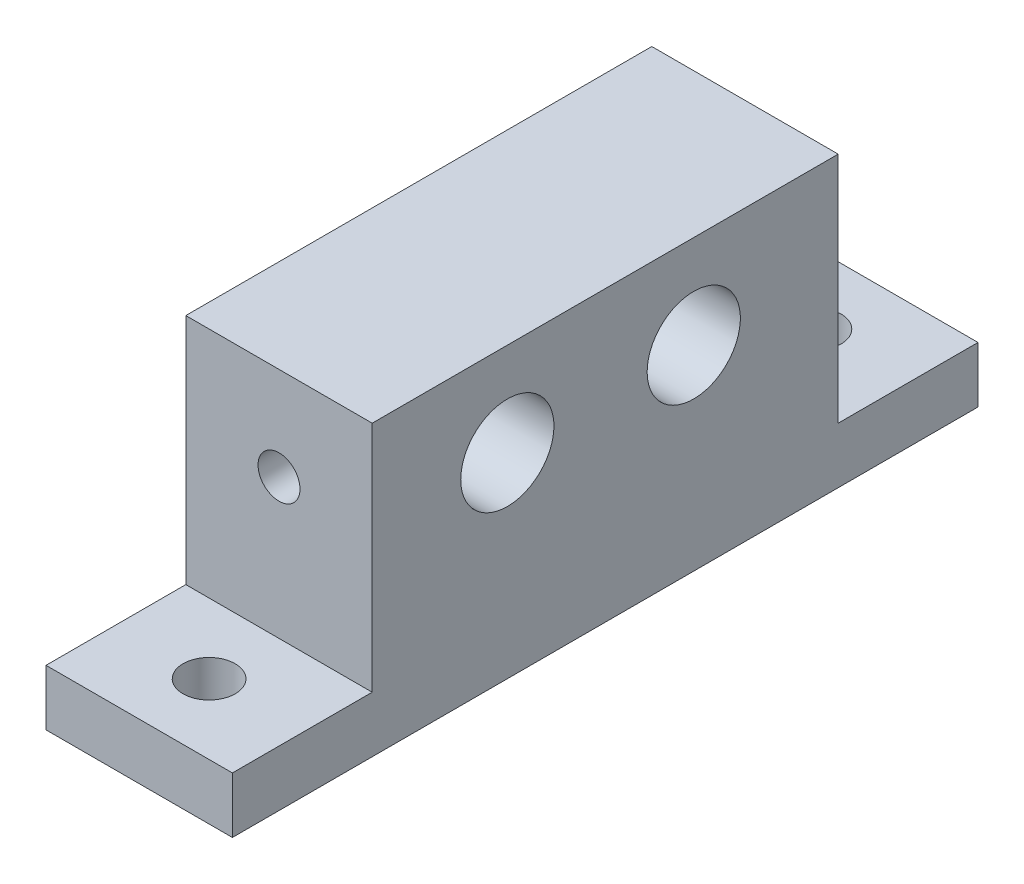
SolidWorks part; units mm, degrees
ref_plane "정면" through (0, 0, 0) normal (0, 0, 1) x (1, 0, 0)
ref_plane "윗면" through (0, 0, 0) normal (0, 1, 0) x (1, 0, 0)
ref_plane "우측면" through (0, 0, 0) normal (1, 0, 0) x (0, 0, -1)
sketch "스케치1" plane through (0, 0, 0) normal (0, 1, 0) x (1, 0, 0)
  line L1 (-9.094, 23.104) -> (0.906, 23.104)
  line L2 (-9.094, 23.104) -> (-9.094, -1.896)
  line L3 (-9.094, -1.896) -> (0.906, -1.896)
  line L4 (0.906, 23.104) -> (0.906, -1.896)
  line L5 (-9.094, 23.104) -> (0.906, -1.896) construction
  line L6 (-9.094, -1.896) -> (0.906, 23.104) construction
  point P0 (-4.094, 10.604)
  dimension "D1" = 25
  dimension "D2" = 10
extrude "보스-돌출1" add sketch "스케치1" along normal blind 10
sketch "스케치2" plane through (-9.094, 0, 0) normal (-1, 0, 0) x (0, 0, 1)
  line L0 (1.896, 10) -> (1.896, 0) construction
  line L1 (-23.104, 10) -> (1.896, 10) construction
  circle A0 centre (-5.354, 5) radius 2.5
  circle A1 centre (-15.354, 5) radius 2.5
  dimension "D1" = 5
  dimension "D2" = 5
  dimension "D5" = 5
  dimension "D6" = 5
  dimension "D3" = 10
  dimension "D4" = 7.25
extrude "컷-돌출1" cut sketch "스케치2" against normal blind 10
sketch "스케치3" plane through (0, 0, 1.896) normal (0, 0, 1) x (1, 0, 0)
  line L0 (0.906, 10) -> (0.906, 0) construction
  line L3 (-9.094, 0) -> (0.906, 0) construction
  circle A0 centre (-4.094, 5) radius 1.125
  dimension "D1" = 5
  dimension "D3" = 2.25
  dimension "D2" = 5
extrude "컷-돌출2" cut sketch "스케치3" against normal up to surface (4.75 mm away) up to face at (0.906, 5, -2.854)
sketch "스케치4" plane through (0, 0, -23.104) normal (0, 0, -1) x (-1, 0, 0)
  line L0 (-0.906, 0) -> (9.094, 0) construction
  line L1 (-0.906, 10) -> (-0.906, 0) construction
  circle A0 centre (4.094, 5) radius 1.125
  dimension "D1" = 2.25
  dimension "D2" = 5
  dimension "D3" = 5
extrude "컷-돌출3" cut sketch "스케치4" against normal up to surface (5.25 mm away) up to face at (0.906, 5, -12.854)
sketch "스케치5" plane through (0, 0, 0) normal (0, -1, 0) x (1, 0, 0)
  line L0 (0.906, 1.896) -> (0.906, -23.104) construction
  line L1 (0.906, 1.896) -> (-9.094, 1.896)
  line L2 (0.906, 1.896) -> (0.906, -23.104)
  line L3 (0.906, -23.104) -> (-9.094, -23.104)
  line L4 (-9.094, 1.896) -> (-9.094, -23.104)
  line L5 (-9.094, -23.104) -> (-9.094, 1.896) construction
  line L6 (0.906, -23.104) -> (-9.094, -23.104) construction
  dimension "D1" = 25
  dimension "D2" = 0
extrude "보스-돌출2" add sketch "스케치5" along normal blind 2.5
sketch "스케치6" plane through (0, -2.5, 0) normal (0, -1, 0) x (1, 0, 0)
  line L0 (0.906, -23.104) -> (0.906, 1.896) construction
  line L1 (0.906, -30.604) -> (-9.094, -30.604)
  line L2 (0.906, -30.604) -> (0.906, 9.396)
  line L3 (0.906, 9.396) -> (-9.094, 9.396)
  line L4 (-9.094, -30.604) -> (-9.094, 9.396)
  line L5 (-9.094, 1.896) -> (-9.094, -23.104) construction
  line L6 (0.906, 1.896) -> (-9.094, 1.896) construction
  dimension "D1" = 40
  dimension "D2" = 7.5
extrude "보스-돌출3" add sketch "스케치6" along normal blind 3
sketch "스케치7" plane through (0, -2.5, 0) normal (0, 1, 0) x (1, 0, 0)
  line L0 (0.906, 30.604) -> (0.906, 23.104) construction
  line L1 (0.906, -1.896) -> (0.906, -9.396) construction
  line L4 (0.906, -9.396) -> (-9.094, -9.396) construction
  line L5 (-9.094, 30.604) -> (0.906, 30.604) construction
  circle A0 centre (-4.094, -5.646) radius 1.4
  circle A1 centre (-4.094, 26.854) radius 1.4
  dimension "D1" = 2.8
  dimension "D2" = 2.8
  dimension "D5" = 3.75
  dimension "D6" = 3.75
  dimension "D3" = 5
  dimension "D4" = 5
extrude "컷-돌출4" cut sketch "스케치7" against normal up to surface (3 mm away) up to face at (-4.094, -5.5, -10.604)
